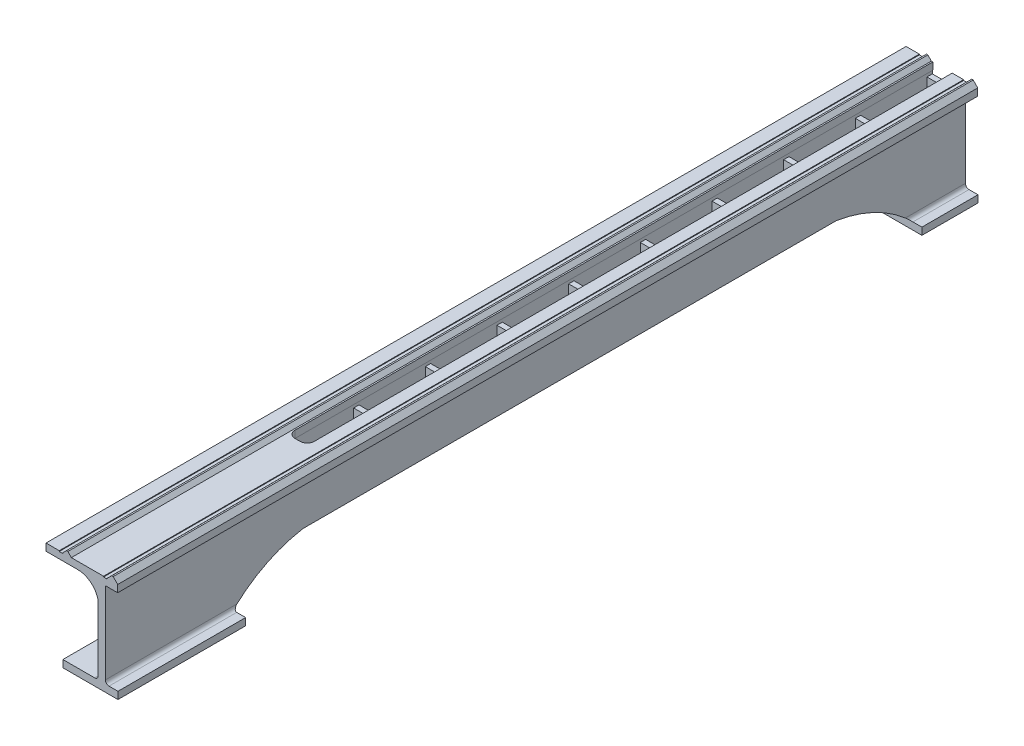
SolidWorks part; units mm, degrees
ref_plane "Front Plane" through (0, 0, 0) normal (0, 0, 1) x (1, 0, 0)
ref_plane "Top Plane" through (0, 0, 0) normal (0, 1, 0) x (1, 0, 0)
ref_plane "Right Plane" through (0, 0, 0) normal (1, 0, 0) x (0, 0, -1)
sketch "Sketch1" plane through (0, 0, 0) normal (0, 0, 1) x (1, 0, 0)
  line L0 (-31.5551, 31.2902) -> (-37.8538, 37.7187)
  line L2 (-131.555, 31.42) -> (-131.555, 21.42)
  line L4 (-31.5551, 31.2902) -> (-31.5551, 21.2902)
  line L5 (-37.8538, 37.7187) -> (-39.8538, 37.7187)
  line L6 (-39.8538, 37.7187) -> (-46.2824, 31.42)
  line L7 (-46.2824, 31.42) -> (-46.2824, 30.42)
  line L8 (-46.2824, 30.42) -> (-51.2824, 30.42)
  line L9 (-51.2824, 30.42) -> (-51.2824, 31.42)
  line L10 (-51.2824, 31.42) -> (-96.2063, 31.42)
  line L14 (-96.2063, 31.42) -> (-101.1053, 36.42)
  line L15 (-101.1053, 36.42) -> (-103.1053, 36.42)
  line L16 (-103.1053, 36.42) -> (-108.055, 31.4703)
  line L17 (-108.055, 31.4703) -> (-108.055, 30.42)
  line L18 (-108.055, 30.42) -> (-113.055, 30.42)
  line L19 (-113.055, 30.42) -> (-113.055, 31.42)
  line L20 (-113.055, 31.42) -> (-131.555, 31.42)
  line L21 (-131.555, 21.42) -> (-87.3496, 21.42)
  line L22 (-31.5551, 21.2902) -> (-48.7011, 21.2902)
  line L23 (-48.7011, 21.2902) -> (-48.7011, -92.58)
  line L24 (-43.7011, -97.58) -> (-31.1954, -97.58)
  line L25 (-31.1954, -97.58) -> (-31.1954, -107.58)
  line L26 (-31.1954, -107.58) -> (-108.01, -107.58)
  line L27 (-108.01, -107.58) -> (-108.01, -97.58)
  line L28 (-108.01, -97.58) -> (-63.7011, -97.58)
  line L29 (-58.7011, -92.58) -> (-58.7011, -1.9527)
  arc A0 (-87.3496, 21.42) -> (-58.7011, -1.9527) centre (-87.3496, -7.8239) cw
  arc A1 (-48.7011, -92.58) -> (-43.7011, -97.58) centre (-43.7011, -92.58) ccw
  arc A2 (-63.7011, -97.58) -> (-58.7011, -92.58) centre (-63.7011, -92.58) ccw
  point P30 (-48.7011, -97.58)
  dimension "D17" = 5
  dimension "D1" = 100
  dimension "D2" = 7
  dimension "D3" = 2
  dimension "D4" = 5
  dimension "D5" = 18.5
  dimension "D6" = 5
  dimension "D7" = 10
  dimension "D8" = 135
  dimension "D9" = 9
  dimension "D10" = 9
  dimension "D11" = 2
  dimension "D12" = 7
  dimension "D13" = 10
  dimension "D14" = 5
  dimension "D15" = 10
  dimension "D16" = 139
  dimension "D18" = 10
  dimension "D19" = 1
extrude "Boss-Extrude1" add sketch "Sketch1" along normal blind 1200
sketch "Sketch2" plane through (0, 20.7647, 0) normal (0, 1, 0) x (1, 0, 0)
  line L0 (-94.1707, -1200) -> (-94.1707, 0) construction
  line L1 (-84.1707, 100) -> (-77.1707, 100)
  line L2 (-94.1707, 90) -> (-94.1707, -890)
  line L3 (-84.1707, -900) -> (-77.1707, -900)
  line L4 (-67.1707, 90) -> (-67.1707, -890)
  line L5 (-67.1707, -1200) -> (-67.1707, 0) construction
  line L6 (-51.2824, 0) -> (-96.2063, 0) construction
  arc A0 (-94.1707, -890) -> (-84.1707, -900) centre (-84.1707, -890) ccw
  arc A1 (-77.1707, -900) -> (-67.1707, -890) centre (-77.1707, -890) ccw
  arc A2 (-77.1707, 100) -> (-67.1707, 90) centre (-77.1707, 90) cw
  arc A3 (-84.1707, 100) -> (-94.1707, 90) centre (-84.1707, 90) ccw
  point P12 (-67.1707, -900)
  point P15 (-67.1707, 100)
  point P18 (-94.1707, 100)
  dimension "D2" = 10
  dimension "D1" = 1000
  dimension "D3" = 100
extrude "Cut-Extrude1" cut sketch "Sketch2" along normal blind 800
sketch "Sketch3" plane through (0, 0, 1200) normal (0, 0, 1) x (1, 0, 0)
  line L1 (-57.7636, 8.0977) -> (-93.9675, 8.0977)
  line L2 (-57.7636, 8.0977) -> (-57.7636, 21.2819)
  line L3 (-57.7636, 21.2819) -> (-93.9675, 21.2819)
  line L4 (-93.9675, 8.0977) -> (-93.9675, 21.2819)
extrude "Cut-Extrude2" cut sketch "Sketch3" against normal blind 900 from offset 300 offset against normal yes
sketch "Sketch5" plane through (0, 0, 0) normal (0, 0, -1) x (-1, 0, 0)
  line L1 (105.3464, -97.4955) -> (94.9198, -97.4955)
  line L2 (105.3464, -97.4955) -> (105.3464, 27.7967)
  line L3 (105.3464, 27.7967) -> (94.9198, 27.7967)
  line L4 (94.9198, -97.4955) -> (94.9198, 27.7967)
extrude "Boss-Extrude2" add sketch "Sketch5" against normal blind 1100
sketch "Sketch6" plane through (-105.3464, 0, 0) normal (-1, 0, 0) x (0, 0, 1)
  line L0 (0, -97.4955) -> (0, 21.42) construction
  line L1 (0, 16.5847) -> (7.4351, 16.5847)
  line L2 (0, 16.5847) -> (0, -47.4448)
  line L3 (0, -47.4448) -> (7.4351, -47.4448)
  line L4 (7.4351, 16.5847) -> (7.4351, -47.4448)
extrude "Boss-Extrude3" add sketch "Sketch6" against normal blind 50
pattern_linear "LPattern1" count 10 spacing 100 along (0, 0, 1) of "Boss-Extrude3"
sketch "Sketch4" plane through (-31.5551, 0, 0) normal (1, 0, 0) x (0, 0, -1)
  line L0 (-1021.7946, -97.58) -> (-1021.7946, -107.58)
  line L1 (-1200, -97.58) -> (0, -97.58) construction
  line L2 (-1200, -107.58) -> (0, -107.58) construction
  line L3 (-1021.7946, -107.58) -> (-1021.7946, -177.9566)
  line L4 (-1021.7946, -177.9566) -> (-78.2516, -177.9566)
  line L5 (-78.2516, -177.9566) -> (-78.2516, -97.58)
  line L6 (-924.3184, -47.58) -> (-180.0688, -47.58)
  arc A1 (-924.3184, -47.58) -> (-1021.7946, -97.58) centre (-893.2342, -228.1954) ccw
  arc A2 (-180.0688, -47.58) -> (-78.2516, -97.58) centre (-211.2911, -239.8268) cw
  dimension "D1" = 60
extrude "Cut-Extrude3" cut sketch "Sketch4" against normal blind 100 and the other way blind 10
